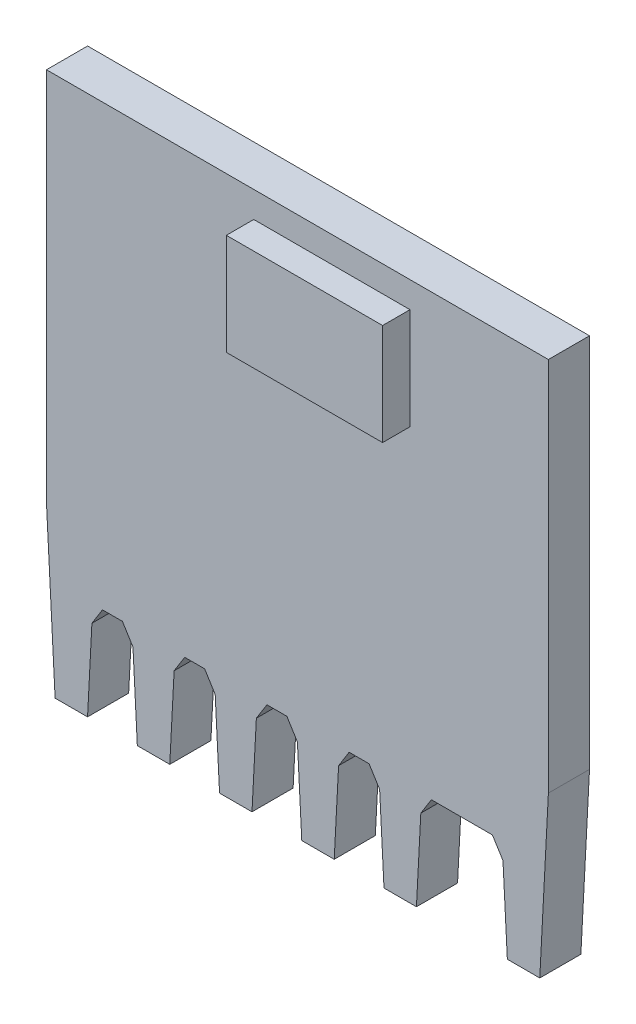
SolidWorks part; units mm, degrees
ref_plane "Front Plane" through (0, 0, 0) normal (0, 0, 1) x (1, 0, 0)
ref_plane "Top Plane" through (0, 0, 0) normal (0, 1, 0) x (1, 0, 0)
ref_plane "Right Plane" through (0, 0, 0) normal (1, 0, 0) x (0, 0, -1)
sketch "Sketch1" plane through (0, 0, 0) normal (0, 0, 1) x (1, 0, 0)
  line L0 (0, 0) -> (0, 19.7) construction
  line L1 (0, 19.7) -> (18.3124, 19.7) construction
  line L2 (18.3124, 19.7) -> (18.3124, 0) construction
  line L3 (18.3124, 0) -> (0, 0) construction
  line L4 (0, 3) -> (18.3124, 3) construction
  line L5 (0, 6) -> (18.3124, 6) construction
  line L6 (0.9062, 6) -> (0.9062, 0) construction
  line L7 (3.9062, 6) -> (3.9062, 0) construction
  line L8 (6.9062, 6) -> (6.9062, 0) construction
  line L9 (9.9062, 6) -> (9.9062, 0) construction
  line L10 (12.9062, 6) -> (12.9062, 0) construction
  line L11 (17.4062, 6) -> (17.4062, 0) construction
  line L12 (0.9062, 3) -> (3.9062, 3) construction
  line L13 (3.9062, 3) -> (6.9062, 3) construction
  line L14 (6.9062, 3) -> (9.9062, 3) construction
  line L15 (9.9062, 3) -> (12.9062, 3) construction
  line L16 (12.9062, 3) -> (17.4062, 3) construction
  line L17 (0.9062, 3) -> (0, 3) construction
  line L18 (17.4062, 3) -> (18.3124, 3) construction
  line L19 (2.4062, 3) -> (2.4062, 0) construction
  line L20 (5.4062, 3) -> (5.4062, 0) construction
  line L21 (8.4062, 3) -> (8.4062, 0) construction
  line L22 (11.4062, 3) -> (11.4062, 0) construction
  line L23 (15.1562, 3) -> (15.1562, 0) construction
  line L24 (14.4062, 3.75) -> (15.9062, 3.75) construction
  line L25 (0, 6) -> (0.3144, 0)
  line L26 (0.3144, 0) -> (1.4979, 0)
  line L27 (1.4979, 0) -> (1.6572, 3.0393)
  line L28 (3.1552, 3.0393) -> (3.3144, 0)
  line L29 (3.3144, 0) -> (4.4979, 0)
  line L30 (4.4979, 0) -> (4.6572, 3.0393)
  line L31 (6.1552, 3.0393) -> (6.3144, 0)
  line L32 (6.3144, 0) -> (7.4979, 0)
  line L33 (7.4979, 0) -> (7.6572, 3.0393)
  line L34 (9.1552, 3.0393) -> (9.3144, 0)
  line L35 (9.3144, 0) -> (10.4979, 0)
  line L36 (10.4979, 0) -> (10.6572, 3.0393)
  line L37 (12.1552, 3.0393) -> (12.3144, 0)
  line L38 (12.3144, 0) -> (13.4979, 0)
  line L39 (13.4979, 0) -> (13.6572, 3.0393)
  line L40 (16.6552, 3.0393) -> (16.8144, 0)
  line L41 (16.8144, 0) -> (17.9979, 0)
  line L42 (17.9979, 0) -> (18.3124, 6)
  line L44 (1.6572, 3.0393) -> (2.0426, 3.656)
  line L45 (0, 6) -> (0, 19.7)
  line L46 (0, 19.7) -> (18.3124, 19.7)
  line L47 (18.3124, 19.7) -> (18.3124, 6)
  line L48 (9.1562, 19.7) -> (9.1562, 6) construction
  line L49 (2.0426, 3.656) -> (2.7698, 3.656)
  line L50 (2.7698, 3.656) -> (3.1552, 3.0393)
  line L51 (4.6572, 3.0393) -> (5.0426, 3.656)
  line L52 (5.0426, 3.656) -> (5.7698, 3.656)
  line L53 (5.7698, 3.656) -> (6.1552, 3.0393)
  line L54 (7.6572, 3.0393) -> (8.0426, 3.656)
  line L55 (8.0426, 3.656) -> (8.7698, 3.656)
  line L56 (8.7698, 3.656) -> (9.1552, 3.0393)
  line L57 (10.6572, 3.0393) -> (11.0426, 3.656)
  line L58 (11.0426, 3.656) -> (11.7698, 3.656)
  line L59 (11.7698, 3.656) -> (12.1552, 3.0393)
  line L60 (13.6572, 3.0393) -> (14.0426, 3.656)
  line L61 (14.0426, 3.656) -> (16.2698, 3.656)
  line L62 (16.2698, 3.656) -> (16.6552, 3.0393)
  arc A0 (3.1552, 3.0393) -> (1.6572, 3.0393) centre (2.4062, 3) ccw construction
  arc A1 (6.1552, 3.0393) -> (4.6572, 3.0393) centre (5.4062, 3) ccw construction
  arc A2 (9.1552, 3.0393) -> (7.6572, 3.0393) centre (8.4062, 3) ccw construction
  arc A3 (12.1552, 3.0393) -> (10.6572, 3.0393) centre (11.4062, 3) ccw construction
  arc A4 (13.6572, 3.0393) -> (14.4062, 3.75) centre (14.4062, 3) cw construction
  arc A5 (16.6552, 3.0393) -> (15.9062, 3.75) centre (15.9062, 3) ccw construction
  dimension "D7" = 0.75
  dimension "D1" = 3
  dimension "D2" = 6
  dimension "D3" = 13.7
  dimension "D4" = 3
  dimension "D6" = 4.5
  dimension "D8" = 3
  dimension "D9" = 18.3124
  dimension "D10" = 19.7
extrude "Boss-Extrude1" add sketch "Sketch1" along normal blind 1.5
sketch "Sketch3" plane through (0, 0, 0) normal (0, 0, 1) x (1, 0, 0)
  line L0 (-0.4005, 6) -> (18.7129, 6)
  line L1 (18.7129, 3) -> (-0.4005, 3) construction
  line L2 (-0.4005, 0) -> (18.7129, 0) construction
  line L3 (-0.4005, -0.5) -> (18.7129, -0.5) construction
  line L4 (18.7129, -0.5) -> (18.7129, 6) construction
  line L5 (-0.4005, 6) -> (-0.4005, -0.5) construction
  line L6 (18.3124, 0) -> (0, 0) construction
  line L7 (0, 3) -> (18.3124, 3) construction
  line L8 (0, 6) -> (18.3124, 6) construction
  line L9 (0.3407, -0.5) -> (0, 6) construction
  line L10 (18.3124, 6) -> (17.9717, -0.5) construction
  line L11 (17.9979, 0) -> (18.3124, 6) construction
  line L12 (0, 6) -> (0.3144, 0) construction
  line L13 (5.4062, 6) -> (5.4062, -0.5) construction
  line L14 (3.9062, 6) -> (3.9062, -0.5) construction
  line L15 (5.4062, 3) -> (5.4062, 0) construction
  line L16 (3.1572, 3) -> (3.3407, -0.5) construction
  line L17 (2.7567, 3) -> (2.9401, -0.5)
  line L18 (3.1552, 3.0393) -> (3.3144, 0) construction
  line L19 (2.9401, -0.5) -> (4.8723, -0.5)
  line L20 (4.8723, -0.5) -> (5.0557, 3)
  line L21 (2.8484, 1.25) -> (3.2478, 1.2709) construction
  line L22 (5.9401, -0.5) -> (5.7567, 3)
  line L26 (7.8723, -0.5) -> (5.9401, -0.5)
  line L27 (8.0557, 3) -> (7.8723, -0.5)
  line L30 (2.4062, -0.5) -> (2.4062, 6) construction
  line L31 (2.4062, 3) -> (2.4062, 0) construction
  line L32 (8.4062, 6) -> (8.4062, -0.5) construction
  line L34 (11.4062, -0.5) -> (11.4062, 6) construction
  line L35 (15.1562, -0.5) -> (15.1562, 6) construction
  line L36 (8.4062, 3) -> (8.4062, 0) construction
  line L37 (11.4062, 3) -> (11.4062, 0) construction
  line L38 (15.1562, 3) -> (15.1562, 0) construction
  line L39 (10.8723, -0.5) -> (11.0557, 3)
  line L40 (8.9401, -0.5) -> (10.8723, -0.5)
  line L41 (8.7567, 3) -> (8.9401, -0.5)
  line L42 (11.9401, -0.5) -> (11.7567, 3)
  line L43 (13.8723, -0.5) -> (11.9401, -0.5)
  line L44 (14.0557, 3) -> (13.8723, -0.5)
  line L45 (16.4401, -0.5) -> (18.3723, -0.5)
  line L46 (16.2567, 3) -> (16.4401, -0.5)
  line L47 (18.3723, -0.5) -> (18.7129, 6)
  line L48 (1.8723, -0.5) -> (-0.0599, -0.5)
  line L49 (2.0557, 3) -> (1.8723, -0.5)
  line L50 (-0.0599, -0.5) -> (-0.4005, 6)
  line L51 (16.2567, 3) -> (14.0557, 3)
  line L52 (11.7567, 3) -> (11.0557, 3)
  line L53 (8.7567, 3) -> (8.0557, 3)
  line L54 (5.7567, 3) -> (5.0557, 3)
  line L55 (2.7567, 3) -> (2.0557, 3)
  dimension "D1" = 0.5
  dimension "D2" = 0.4
ref_plane "Plane1" through (3.9062, 0, 0) normal (1, 0, 0) x (0, 0, -1)
sketch "Sketch4" plane through (3.9062, 0, 0) normal (1, 0, 0) x (0, 0, -1)
  line L0 (0, 6) -> (0, -0.5) construction
  line L1 (0.6, 6) -> (-2.1, 6) construction
  line L2 (0.6, 6) -> (0.6, -0.5) construction
  line L3 (0.6, -0.5) -> (-2.1, -0.5) construction
  line L4 (-2.1, 6) -> (-2.1, -0.5) construction
  line L5 (-0.75, -0.5) -> (-0.75, 6) construction
  line L6 (-1.5, 6) -> (-1.5, -0.5) construction
  line L7 (0.6, 2.4005) -> (-2.1, 2.4005) construction
  line L8 (0.3, 6) -> (0.3, -0.5) construction
  line L9 (0.6, 2.4005) -> (3.846, 6) construction
  line L10 (2.2302, 6) -> (0.6, 4.1923) construction
  line L11 (0.6, 4.1923) -> (1.7139, 3.1878) construction
  line L12 (1.7139, 3.1878) -> (4.25, 6)
  line L13 (4.25, 6) -> (0.6, 6) construction
  line L14 (0.3, 1) -> (-1.8, 1) construction
  line L15 (-2.1, 0) -> (0.6, 0) construction
  line L16 (1.7139, 3.1878) -> (1.4912, 3.3887)
  line L17 (1.4912, 3.3887) -> (0.6, 2.4005)
  line L18 (-3.2139, 3.1878) -> (-5.75, 6)
  line L19 (-3.2139, 3.1878) -> (-2.9912, 3.3887)
  line L20 (-2.9912, 3.3887) -> (-2.1, 2.4005)
  line L21 (-2.1, 6) -> (-5.75, 6) construction
  line L22 (0.6, 3.0724) -> (3.2401, 6) construction
  arc A0 (0.4965, 2.2224) -> (0.6, -0.5) centre (4.2, 1) ccw
  arc A1 (0.6, 2.4005) -> (0.4965, 2.2224) centre (0.9713, 2.0656) ccw
  arc A2 (-2.1, 2.4005) -> (-1.9965, 2.2224) centre (-2.4713, 2.0656) cw
  arc A3 (-1.9965, 2.2224) -> (-2.1, -0.5) centre (-5.7, 1) cw
  dimension "D6" = 0.5
  dimension "D1" = 0.6
  dimension "D2" = 0.3
  dimension "D3" = 1.5
  dimension "D4" = 1
  dimension "D5" = 0.3
  dimension "D7" = 10
sketch "Sketch5" plane through (0, 0, 0) normal (1, 0, 0) x (0, 0, -1)
  line L0 (2.2302, 6) -> (0.6, 4.1923) construction
  line L1 (0.6, 4.1923) -> (1.7139, 3.1878) construction
  line L2 (1.7139, 3.1878) -> (4.25, 6) construction
  line L3 (2.2302, 6) -> (0.6, 4.1923) construction
  line L4 (0.6, 4.1923) -> (1.7139, 3.1878) construction
  line L5 (1.7139, 3.1878) -> (4.25, 6) construction
ref_plane "Plane2" through (0, 2.6105, -2.3541) normal (0, 0.7426, -0.6697) x (1, 0, 0)
sketch "Sketch6" plane through (0, 2.6105, -2.3541) normal (0, 0.7426, -0.6697) x (1, 0, 0)
  line L1 (3.9062, -2.362) -> (3.9062, -0.862) construction
  line L2 (3.9062, -2.362) -> (3.9062, -5.0612) construction
  line L3 (4.6562, -5.0612) -> (3.1562, -5.0612)
  line L4 (4.6562, -1.612) -> (3.1562, -1.612) construction
  line L5 (3.1562, -1.612) -> (3.1562, -5.0612)
  line L6 (4.6562, -1.612) -> (4.6562, -5.0612)
  line L10 (2.4062, -5.0612) -> (15.1562, -5.0612) construction
  line L11 (15.1562, -5.0612) -> (15.1562, -0.862) construction
  line L12 (15.1562, -0.862) -> (2.4062, -0.862) construction
  line L13 (2.4062, -0.862) -> (2.4062, -5.0612) construction
  line L14 (15.1562, 0.3349) -> (15.1562, -4.0182) construction
  line L15 (2.4062, 0.3349) -> (2.4062, -4.0182) construction
  line L16 (11.4062, -5.0612) -> (11.4062, -0.862) construction
  line L17 (8.4062, -5.0612) -> (8.4062, -0.862) construction
  line L18 (5.4062, -5.0612) -> (5.4062, -0.862) construction
  line L19 (5.4062, -4.0182) -> (5.4062, 0.3349) construction
  line L20 (8.4062, -4.0182) -> (8.4062, 0.3349) construction
  line L21 (11.4062, 0.3349) -> (11.4062, -4.0182) construction
  line L22 (0.1562, -1.612) -> (0.1562, -5.0612)
  line L23 (0.1562, -5.0612) -> (1.6562, -5.0612)
  line L24 (1.6562, -1.612) -> (1.6562, -5.0612)
  line L25 (7.6562, -1.612) -> (7.6562, -5.0612)
  line L26 (6.1562, -5.0612) -> (7.6562, -5.0612)
  line L27 (6.1562, -1.612) -> (6.1562, -5.0612)
  line L28 (10.6562, -1.612) -> (10.6562, -5.0612)
  line L29 (10.6562, -5.0612) -> (9.1562, -5.0612)
  line L30 (9.1562, -1.612) -> (9.1562, -5.0612)
  line L31 (13.6562, -1.612) -> (13.6562, -5.0612)
  line L32 (12.1562, -5.0612) -> (13.6562, -5.0612)
  line L33 (12.1562, -1.612) -> (12.1562, -5.0612)
  line L34 (18.1562, -1.612) -> (18.1562, -5.0612)
  line L35 (18.1562, -5.0612) -> (16.6562, -5.0612)
  line L36 (16.6562, -1.612) -> (16.6562, -5.0612)
  circle A0 centre (3.9062, -1.612) radius 0.75 construction
  arc A1 (4.6562, -1.612) -> (3.1562, -1.612) centre (3.9062, -1.612) ccw
  arc A2 (0.1562, -1.612) -> (1.6562, -1.612) centre (0.9062, -1.612) cw
  arc A3 (6.1562, -1.612) -> (7.6562, -1.612) centre (6.9062, -1.612) cw
  arc A4 (10.6562, -1.612) -> (9.1562, -1.612) centre (9.9062, -1.612) ccw
  arc A5 (12.1562, -1.612) -> (13.6562, -1.612) centre (12.9062, -1.612) cw
  arc A6 (18.1562, -1.612) -> (16.6562, -1.612) centre (17.4062, -1.612) ccw
ref_plane "Plane3" through (0, 1.6223, -1.463) normal (0, 0.7426, -0.6697) x (1, 0, 0)
sketch "Sketch7" plane through (0, 1.6223, -1.463) normal (0, 0.7426, -0.6697) x (1, 0, 0)
  line L0 (3.1562, -1.612) -> (3.1562, -5.0612) construction
  line L1 (4.6562, -5.0612) -> (3.1562, -5.0612) construction
  line L2 (4.6562, -1.612) -> (4.6562, -5.0612) construction
  line L3 (3.1562, -1.612) -> (3.1562, -5.0612) construction
  line L4 (4.6562, -5.0612) -> (3.1562, -5.0612) construction
  line L5 (4.6562, -1.612) -> (4.6562, -5.0612) construction
  line L6 (3.9062, -0.862) -> (3.9062, -5.0612) construction
  line L7 (4.6562, -1.612) -> (3.1562, -1.612) construction
  line L8 (4.6562, -2.362) -> (3.1562, -2.362) construction
  line L9 (3.4562, -1.612) -> (3.4562, -2.362)
  line L10 (3.4562, -2.362) -> (4.3562, -2.362)
  line L11 (4.3562, -2.362) -> (4.3562, -1.612)
  line L12 (2.4062, -0.862) -> (2.4062, -5.0612) construction
  line L13 (2.4062, -5.0612) -> (15.1562, -5.0612) construction
  line L14 (15.1562, -0.862) -> (2.4062, -0.862) construction
  line L15 (5.4062, -5.0612) -> (5.4062, -0.862) construction
  line L16 (8.4062, -5.0612) -> (8.4062, -0.862) construction
  line L17 (11.4062, -5.0612) -> (11.4062, -0.862) construction
  line L18 (15.1562, -5.0612) -> (15.1562, -0.862) construction
  line L19 (2.4062, -0.862) -> (2.4062, -5.0612) construction
  line L20 (2.4062, -5.0612) -> (15.1562, -5.0612) construction
  line L21 (15.1562, -0.862) -> (2.4062, -0.862) construction
  line L22 (5.4062, -5.0612) -> (5.4062, -0.862) construction
  line L23 (8.4062, -5.0612) -> (8.4062, -0.862) construction
  line L24 (11.4062, -5.0612) -> (11.4062, -0.862) construction
  line L25 (15.1562, -5.0612) -> (15.1562, -0.862) construction
  line L26 (0.4562, -2.362) -> (0.4562, -1.612)
  line L27 (1.3562, -2.362) -> (0.4562, -2.362)
  line L28 (1.3562, -1.612) -> (1.3562, -2.362)
  line L29 (7.3562, -2.362) -> (6.4562, -2.362)
  line L30 (7.3562, -1.612) -> (7.3562, -2.362)
  line L31 (6.4562, -2.362) -> (6.4562, -1.612)
  line L32 (9.4562, -1.612) -> (9.4562, -2.362)
  line L33 (10.3562, -2.362) -> (10.3562, -1.612)
  line L34 (9.4562, -2.362) -> (10.3562, -2.362)
  line L35 (13.3562, -1.612) -> (13.3562, -2.362)
  line L36 (12.4562, -2.362) -> (12.4562, -1.612)
  line L37 (13.3562, -2.362) -> (12.4562, -2.362)
  line L38 (16.9562, -1.612) -> (16.9562, -2.362)
  line L39 (17.8562, -2.362) -> (17.8562, -1.612)
  line L40 (16.9562, -2.362) -> (17.8562, -2.362)
  arc A0 (4.6562, -1.612) -> (3.1562, -1.612) centre (3.9062, -1.612) ccw construction
  arc A1 (4.6562, -1.612) -> (3.1562, -1.612) centre (3.9062, -1.612) ccw construction
  circle A2 centre (3.9062, -1.612) radius 0.45 construction
  arc A3 (4.3562, -1.612) -> (3.4562, -1.612) centre (3.9062, -1.612) ccw
  arc A4 (0.4562, -1.612) -> (1.3562, -1.612) centre (0.9062, -1.612) cw
  arc A5 (6.4562, -1.612) -> (7.3562, -1.612) centre (6.9062, -1.612) cw
  arc A6 (10.3562, -1.612) -> (9.4562, -1.612) centre (9.9062, -1.612) ccw
  arc A7 (12.4562, -1.612) -> (13.3562, -1.612) centre (12.9062, -1.612) cw
  arc A8 (17.8562, -1.612) -> (16.9562, -1.612) centre (17.4062, -1.612) ccw
ref_plane "bisect" through (0, 0, 0.75) normal (0, 0, 1) x (1, 0, 0)
ref_plane "insert_surface" through (0, 6, 0) normal (0, 1, 0) x (1, 0, 0)
sketch "Sketch8" plane through (0, 6, 0) normal (0, 1, 0) x (1, 0, 0)
  line L0 (18.7129, -0.75) -> (-0.4005, -0.75) construction
  line L1 (-0.4005, 0.6) -> (18.7129, 0.6)
  line L2 (-0.4005, 0.6) -> (-0.4005, -2.1)
  line L3 (-0.4005, -2.1) -> (18.7129, -2.1)
  line L4 (18.7129, 0.6) -> (18.7129, -2.1)
  line L5 (9.1562, 0.6) -> (9.1562, -2.1) construction
  line L6 (0, 0) -> (18.3124, 0) construction
  line L7 (0, 0) -> (0, -1.5) construction
  line L8 (0, -1.5) -> (18.3124, -1.5) construction
  line L9 (18.3124, 0) -> (18.3124, -1.5) construction
  line L10 (18.7129, 0.3) -> (-0.4005, 0.3) construction
  line L11 (18.7129, -1.8) -> (-0.4005, -1.8) construction
sketch "Sketch9" plane through (0, 0, 0) normal (0, 0, 1) x (1, 0, 0)
  line L0 (18.3723, -0.5) -> (18.7129, 6) construction
  line L1 (-0.4005, 6) -> (18.7129, 6) construction
  line L2 (-0.0599, -0.5) -> (-0.4005, 6) construction
  line L3 (1.8723, -0.5) -> (-0.0599, -0.5) construction
  line L4 (2.0557, 3) -> (1.8723, -0.5) construction
  line L5 (2.7567, 3) -> (2.0557, 3) construction
  line L6 (2.7567, 3) -> (2.9401, -0.5) construction
  line L7 (2.9401, -0.5) -> (4.8723, -0.5) construction
  line L8 (4.8723, -0.5) -> (5.0557, 3) construction
  line L9 (5.7567, 3) -> (5.0557, 3) construction
  line L10 (5.9401, -0.5) -> (5.7567, 3) construction
  line L11 (7.8723, -0.5) -> (5.9401, -0.5) construction
  line L12 (8.0557, 3) -> (7.8723, -0.5) construction
  line L13 (8.7567, 3) -> (8.0557, 3) construction
  line L14 (8.7567, 3) -> (8.9401, -0.5) construction
  line L15 (8.9401, -0.5) -> (10.8723, -0.5) construction
  line L16 (10.8723, -0.5) -> (11.0557, 3) construction
  line L17 (11.7567, 3) -> (11.0557, 3) construction
  line L18 (11.9401, -0.5) -> (11.7567, 3) construction
  line L19 (13.8723, -0.5) -> (11.9401, -0.5) construction
  line L20 (14.0557, 3) -> (13.8723, -0.5) construction
  line L21 (16.2567, 3) -> (14.0557, 3) construction
  line L22 (16.2567, 3) -> (16.4401, -0.5) construction
  line L23 (16.4401, -0.5) -> (18.3723, -0.5) construction
  line L24 (18.3723, -0.5) -> (18.7129, 6)
  line L25 (-0.4005, 6) -> (18.7129, 6) construction
  line L26 (-0.0599, -0.5) -> (-0.4005, 6)
  line L27 (1.8723, -0.5) -> (-0.0599, -0.5)
  line L28 (2.0557, 3) -> (1.8723, -0.5)
  line L29 (2.7567, 3) -> (2.0557, 3) construction
  line L30 (2.7567, 3) -> (2.9401, -0.5)
  line L31 (2.9401, -0.5) -> (4.8723, -0.5)
  line L32 (4.8723, -0.5) -> (5.0557, 3)
  line L33 (5.7567, 3) -> (5.0557, 3) construction
  line L34 (5.9401, -0.5) -> (5.7567, 3)
  line L35 (7.8723, -0.5) -> (5.9401, -0.5)
  line L36 (8.0557, 3) -> (7.8723, -0.5)
  line L37 (8.7567, 3) -> (8.0557, 3) construction
  line L38 (8.7567, 3) -> (8.9401, -0.5)
  line L39 (8.9401, -0.5) -> (10.8723, -0.5)
  line L40 (10.8723, -0.5) -> (11.0557, 3)
  line L41 (11.7567, 3) -> (11.0557, 3) construction
  line L42 (11.9401, -0.5) -> (11.7567, 3)
  line L43 (13.8723, -0.5) -> (11.9401, -0.5)
  line L44 (14.0557, 3) -> (13.8723, -0.5)
  line L45 (16.2567, 3) -> (14.0557, 3) construction
  line L46 (16.2567, 3) -> (16.4401, -0.5)
  line L47 (16.4401, -0.5) -> (18.3723, -0.5)
  line L48 (16.2567, 3) -> (16.2567, 6)
  line L49 (14.0557, 3) -> (14.0557, 6)
  line L50 (11.7567, 3) -> (11.7567, 6)
  line L51 (18.7129, 6) -> (-0.4005, 6) construction
  line L52 (11.0557, 3) -> (11.0557, 6)
  line L53 (-0.4005, 6) -> (18.7129, 6) construction
  line L54 (8.7567, 3) -> (8.7567, 6)
  line L55 (8.0557, 3) -> (8.0557, 6)
  line L58 (5.7567, 3) -> (5.7567, 6)
  line L60 (5.0557, 3) -> (5.0557, 6)
  line L62 (15.1562, -0.5) -> (15.1562, 6) construction
  line L63 (15.1562, -0.5) -> (15.1562, 6) construction
  line L64 (2.7567, 3) -> (2.7567, 6)
  line L65 (2.0557, 3) -> (2.0557, 6)
  line L67 (18.7129, 6) -> (16.2567, 6)
  line L68 (14.0557, 6) -> (11.7567, 6)
  line L69 (11.0557, 6) -> (8.7567, 6)
  line L70 (8.0557, 6) -> (5.7567, 6)
  line L71 (5.0557, 6) -> (2.7567, 6)
  line L72 (2.0557, 6) -> (-0.4005, 6)
sketch "rgb_led" plane through (0, 0, 1.5) normal (0, 0, 1) x (1, 0, 0)
  line L0 (13.2624, 16.9) -> (7.5624, 16.9) construction
  line L1 (0, 6) -> (18.3124, 6) construction
  line L2 (10.4124, 16.9) -> (10.4124, 15.05) construction
  line L3 (10.4124, 19.7) -> (10.4124, 16.9) construction
  line L4 (18.3124, 19.7) -> (18.3124, 6) construction
  line L5 (0, 6) -> (0, 19.7) construction
  line L6 (13.2624, 18.75) -> (7.5624, 18.75)
  line L7 (13.2624, 18.75) -> (13.2624, 15.05)
  line L8 (13.2624, 15.05) -> (7.5624, 15.05)
  line L9 (7.5624, 18.75) -> (7.5624, 15.05)
  line L10 (0, 19.7) -> (18.3124, 19.7) construction
  line L11 (0, 19.7) -> (18.3124, 19.7) construction
  line L16 (0, 6) -> (18.3124, 6) construction
  line L17 (18.3124, 6) -> (18.3124, 19.7) construction
  line L18 (0, 19.7) -> (0, 6) construction
  dimension "D1" = 2.8
  dimension "D2" = 3.7
  dimension "D3" = 5.7
  dimension "D4" = 7.9
extrude "Boss-Extrude2" add sketch "rgb_led" along normal blind 1
sketch "Sketch10" plane through (0, 6, 0) normal (0, 1, 0) x (1, 0, 0)
  line L0 (-0.8438, 0) -> (9.1562, 0) construction
  line L1 (-0.8438, 5) -> (19.1562, 5)
  line L2 (-0.8438, 5) -> (-0.8438, -5)
  line L3 (-0.8438, -5) -> (19.1562, -5)
  line L4 (19.1562, 5) -> (19.1562, -5)
  line L5 (9.1562, 0) -> (19.1562, 0) construction
  line L6 (9.1562, 0) -> (9.1562, 5) construction
  line L7 (9.1562, 0) -> (9.1562, -5) construction
  dimension "D1" = 10
  dimension "D2" = 20
